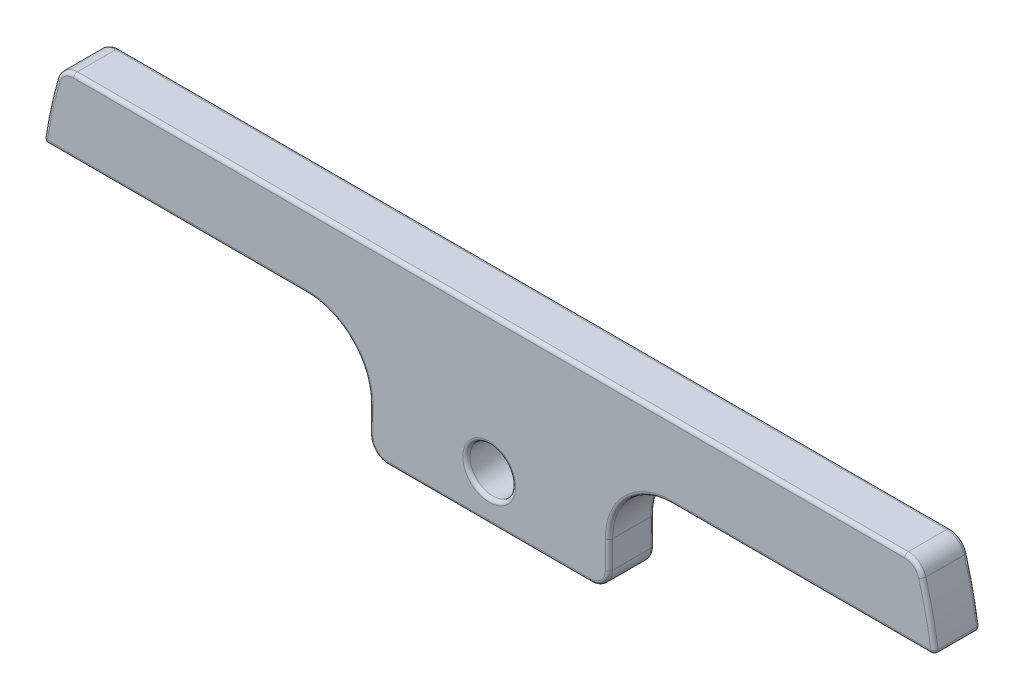
SolidWorks part; units mm, degrees
ref_plane "Front Plane" through (0, 0, 0) normal (0, 0, 1) x (1, 0, 0)
ref_plane "Top Plane" through (0, 0, 0) normal (0, 1, 0) x (1, 0, 0)
ref_plane "Right Plane" through (0, 0, 0) normal (1, 0, 0) x (0, 0, -1)
sketch "Sketch1" plane through (0, 0, 0) normal (0, 0, 1) x (1, 0, 0)
  line L0 (0, 12.7) -> (125.4125, 12.7) construction
  line L1 (0, 0) -> (0.3223, 0)
  line L2 (0, 0) -> (0, 25.4) construction
  line L3 (0, 25.4) -> (125.4125, 25.4) construction
  line L4 (125.4125, 0) -> (125.4125, 25.4) construction
  line L5 (62.7063, 0) -> (62.7063, 25.4) construction
  line L6 (0, 6.35) -> (125.4125, 6.35) construction
  line L7 (0.6108, 15.0812) -> (37.3063, 15.0812)
  line L8 (88.1063, 0) -> (88.1063, 25.4) construction
  line L9 (37.3063, 0) -> (37.3063, 25.4) construction
  line L10 (88.1063, 15.0812) -> (124.8017, 15.0812)
  line L11 (0, 15.0812) -> (125.4125, 15.0812) construction
  line L12 (125.0902, 0) -> (125.4125, 0)
  line L13 (2.9637, 25.4) -> (122.4488, 25.4)
  line L14 (46.0375, 6.35) -> (46.0375, 0)
  line L15 (79.375, 6.35) -> (79.375, 0)
  line L16 (46.0375, 0) -> (79.375, 0)
  circle A0 centre (62.7063, 6.35) radius 3.175
  arc A1 (88.1063, 15.0812) -> (79.375, 6.35) centre (88.1063, 6.35) ccw
  arc A2 (46.0375, 6.35) -> (37.3063, 15.0812) centre (37.3063, 6.35) ccw
  arc A3 (2.9637, 25.4) -> (0.6108, 15.0812) centre (62.7063, 6.35) ccw
  arc A6 (124.8017, 15.0812) -> (122.4488, 25.4) centre (62.7063, 6.35) ccw
  dimension "D3" = 6.35
  dimension "D1" = 25.4
  dimension "D2" = 125.4125
  dimension "D4" = 8.7312
  dimension "D5" = 25.4
  dimension "D6" = 25.4
extrude "Extrude1" add sketch "Sketch1" along normal blind 6.35 contours A3 L7 A2 L14 L16 L15 A1 L10 A6 L13 | A0
fillet "Fillet1" radius 2.54 4 edges at (122.4488, 25.4, 3.175) (2.9637, 25.4, 3.175) (46.0375, 0, 3.175) (79.375, 0, 3.175)
fillet "Fillet2" radius 0.508 32 edges at (65.8813, 6.35, 0) (3.3196, 24.8876, 0) (1.3624, 19.3502, 0) (18.9585, 15.0812, 0) (43.4802, 12.5239, 0) (46.0375, 4.445, 0) (46.7814, 0.7439, 0) (62.7063, 0, 0) (78.6311, 0.7439, 0) (79.375, 4.445, 0) (81.9323, 12.5239, 0) (106.454, 15.0812, 0) (124.0501, 19.3502, 0) (122.0929, 24.8876, 0) (62.7062, 25.4, 0) (65.8813, 6.35, 6.35) (106.454, 15.0812, 6.35) (81.9323, 12.5239, 6.35) (79.375, 4.445, 6.35) (78.6311, 0.7439, 6.35) (62.7063, 0, 6.35) (46.7814, 0.7439, 6.35) (46.0375, 4.445, 6.35) (43.4802, 12.5239, 6.35) (18.9585, 15.0812, 6.35) (1.3624, 19.3502, 6.35) (3.3196, 24.8876, 6.35) (62.7062, 25.4, 6.35) (122.0929, 24.8876, 6.35) (124.0501, 19.3502, 6.35) (124.8017, 15.0812, 3.175) (0.6108, 15.0812, 3.175)
